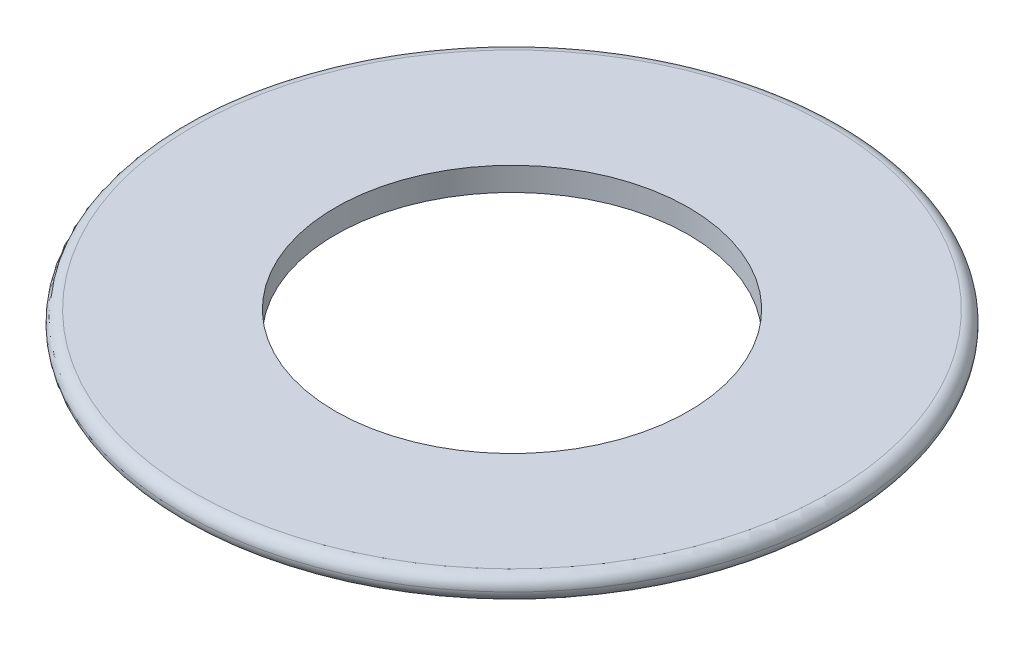
SolidWorks part; units mm, degrees
material "Plain Carbon Steel"
ref_plane "Front Plane" through (0, 0, 0) normal (0, 0, 1) x (1, 0, 0)
ref_plane "Top Plane" through (0, 0, 0) normal (0, 1, 0) x (1, 0, 0)
ref_plane "Right Plane" through (0, 0, 0) normal (1, 0, 0) x (0, 0, -1)
sketch "Sketch1" plane through (0, 0, 0) normal (0, 1, 0) x (1, 0, 0)
  circle A0 centre (0, 0) radius 7.5
  circle A1 centre (0, 0) radius 14
  dimension "D1" = 15
  dimension "D2" = 28
extrude "Boss-Extrude1" add sketch "Sketch1" along normal blind 1
fillet "Fillet1" radius 0.5 2 edges at (0, 0, 14) (0, 1, 14)
